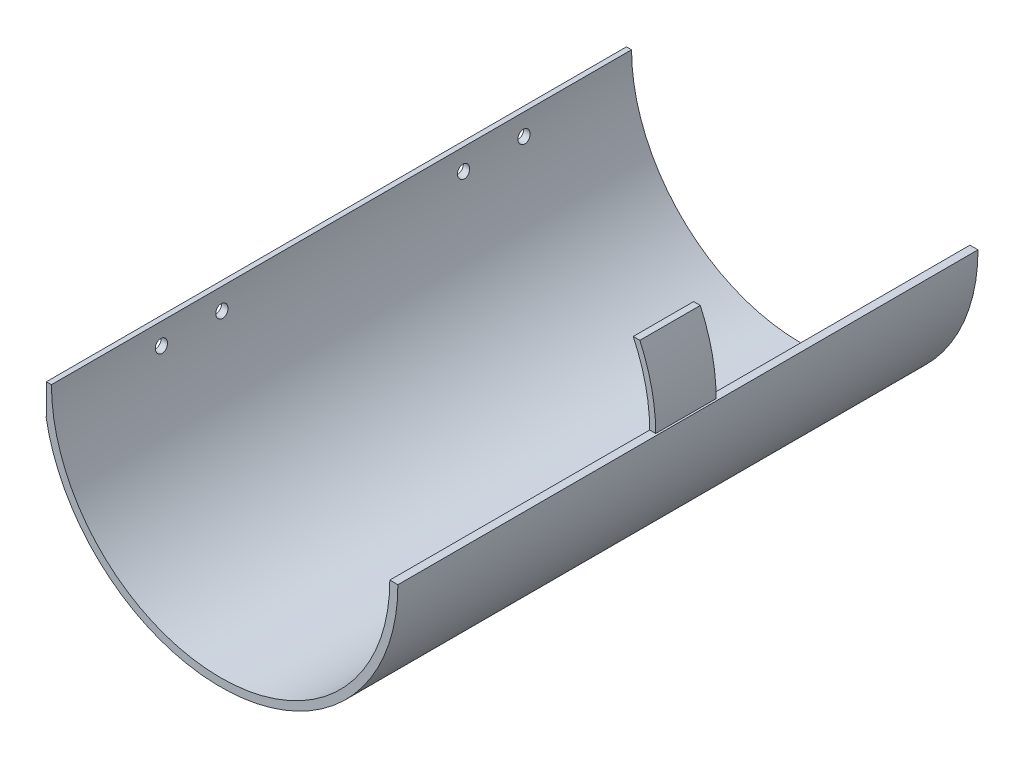
SolidWorks part; units mm, degrees
ref_plane "Front Plane" through (0, 0, 0) normal (0, 0, 1) x (1, 0, 0)
ref_plane "Top Plane" through (0, 0, 0) normal (0, 1, 0) x (1, 0, 0)
ref_plane "Right Plane" through (0, 0, 0) normal (1, 0, 0) x (0, 0, -1)
sketch "Sketch1" plane through (0, 0, 0) normal (0, 0, 1) x (1, 0, 0)
  line L0 (-44, 0) -> (-42, 0)
  line L1 (42, 0) -> (44, 0)
  arc A0 (-44, 0) -> (44, 0) centre (0, 0) ccw
  arc A1 (-42, 0) -> (42, 0) centre (0, 0) ccw
  dimension "D1" = 88
  dimension "D2" = 84
extrude "Boss-Extrude1" add sketch "Sketch1" along normal blind 144
sketch "Sketch2" plane through (0, 0, 0) normal (1, 0, 0) x (0, 0, -1)
  line L0 (-144, 0) -> (-144, -44) construction
  line L1 (0, -44) -> (0, 0) construction
  line L2 (-144, 0) -> (0, 0) construction
  circle A0 centre (-117, -5) radius 1.5
  circle A1 centre (-102, -5) radius 1.5
  circle A2 centre (-42, -5) radius 1.5
  circle A3 centre (-27, -5) radius 1.5
  dimension "D1" = 3
  dimension "D2" = 3
  dimension "D3" = 3
  dimension "D4" = 3
  dimension "D5" = 15
  dimension "D6" = 15
  dimension "D7" = 27
  dimension "D8" = 27
  dimension "D9" = 60
  dimension "D10" = 5
extrude "Cut-Extrude1" cut sketch "Sketch2" against normal up to surface (43.715 mm away) up to face at (0, -22, 72)
ref_plane "Plane1" through (0, 0, 72) normal (0, 0, -1) x (-1, 0, 0)
sketch "Sketch4" plane through (0, 0, 72) normal (0, 0, -1) x (-1, 0, 0)
  line L0 (-39.5677, 18.0735) -> (-37.9124, 18.0735)
  line L1 (-43.5, 0) -> (-42, 0)
  arc A0 (-37.9124, 18.0735) -> (-42, 0) centre (0, 0) ccw
  arc A1 (-39.5677, 18.0735) -> (-43.5, 0) centre (0, 0) ccw
  point P1 (-52.2843, 10.5209)
  dimension "D1" = 87
  dimension "D2" = 84
extrude "Boss-Extrude2" add sketch "Sketch4" along normal blind 7.5 and the other way blind 7.5
sketch "Sketch5" plane through (0, 0, 144) normal (0, 0, 1) x (1, 0, 0)
  line L5 (-44, 0) -> (-44, -7.5543)
  line L6 (-44, -7.5543) -> (-42.7628, -7.5543)
  line L7 (-42.7628, -7.5543) -> (-42.7628, 0)
  line L8 (-42, 0) -> (-44, 0) construction
  line L9 (-42.7628, 0) -> (-44, 0)
extrude "Cut-Extrude2" cut sketch "Sketch5" against normal up to surface (144 mm away) up to face at (0, -21.5, 0)
sketch "Sketch6" plane through (-42.7628, 0, 0) normal (-1, 0, 0) x (0, 0, 1)
  line L1 (0, -7.5543) -> (144, -7.5543)
  line L2 (0, -7.5543) -> (0, 0)
  line L3 (0, 0) -> (144, 0)
  line L4 (144, -7.5543) -> (144, 0)
  circle A0 centre (27, -5) radius 1.5
  circle A1 centre (42, -5) radius 1.5
  circle A2 centre (102, -5) radius 1.5
  circle A3 centre (117, -5) radius 1.5
  circle M5 centre (42, -5) radius 1.5
  circle M6 centre (117, -5) radius 1.5
  line M7 (0, 0) -> (0, -7.5543)
  line M8 (0, -7.5543) -> (144, -7.5543)
  line M9 (144, -7.5543) -> (144, 0)
  line M10 (144, 0) -> (0, 0)
  circle M11 centre (102, -5) radius 1.5
  circle M12 centre (27, -5) radius 1.5
extrude "Boss-Extrude3" add sketch "Sketch6" along normal blind 0.5 contours M10 M7 M8 M9 M6 M11 M12 M5 region at (-42.7628, -3.7445, 72)
